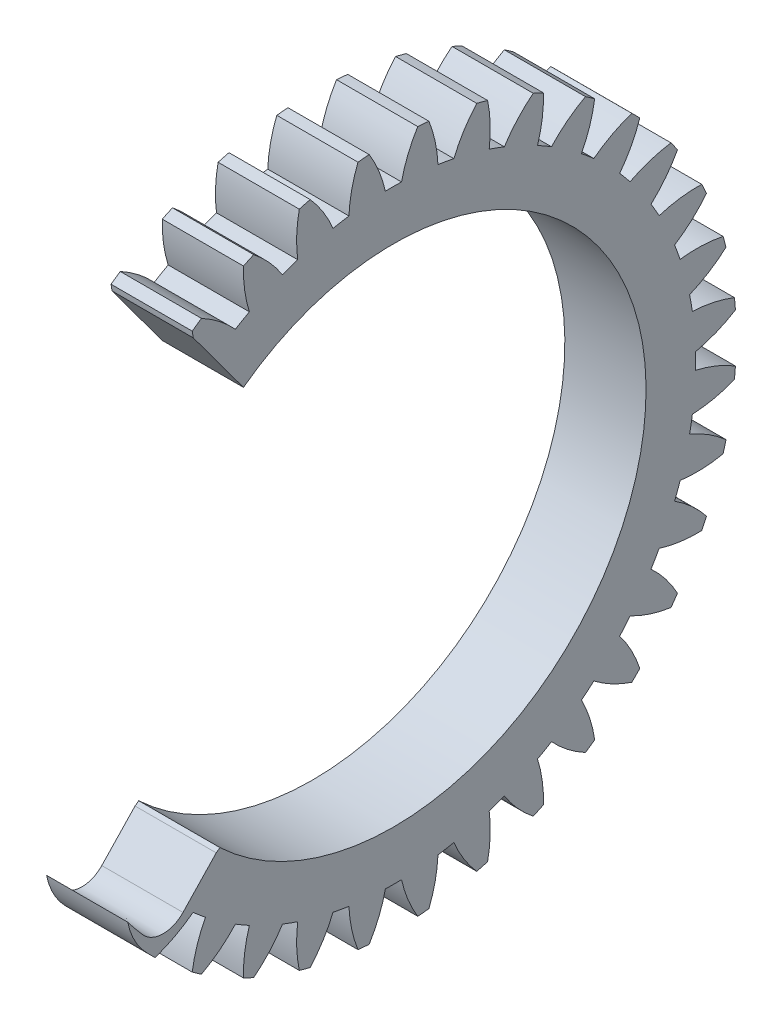
SolidWorks part; units mm, degrees
ref_plane "Plane1" through (0, 0, 0) normal (0, 0, 1) x (1, 0, 0)
ref_plane "Plane2" through (0, 0, 0) normal (0, 1, 0) x (1, 0, 0)
ref_plane "Plane3" through (0, 0, 0) normal (1, 0, 0) x (0, 0, -1)
sketch "HoldingSke" plane through (0, 0, 0) normal (0, 1, 0) x (1, 0, 0)
  line L0 (0, 0) -> (0.4045, -0.2939)
  line L1 (-15, 0) -> (100, 0) construction
  line L2 (0, 0) -> (-2.1039, 2.3779)
  line L3 (0, 0) -> (-11.863, 4.5341)
  line L4 (0, 0) -> (6.9867, 5.0761)
  line L5 (0, 0) -> (-46.8476, -17.4728)
  line L6 (0, 0) -> (-7.4607, -5.0337)
  line L7 (-2.1039, 2.3779) -> (8.6586, 51.2059)
  line L8 (-76.2, 54.61) -> (-71.9, 54.61)
  line L9 (-71.009, 38.7566) -> (-53.1078, 45.2721)
  line L10 (-76.2, 71.12) -> (104.1128, 71.12)
  line L11 (0, 0) -> (-9, 0)
  line L12 (-76.2, 101.6) -> (-76.133, 101.6)
  line L13 (24.9733, 27.94) -> (52.9518, 28.4284)
  line L14 (24.9733, 27.94) -> (24.9743, 27.94)
  line L15 (24.9733, 27.94) -> (100.4006, 29.5858)
  line L16 (-63.627, -2) -> (-12.827, -2)
  circle A0 centre (0, 0) radius 28
  circle A1 centre (0, 0) radius 33.499
  circle A2 centre (0, 0) radius 37.5
  circle A3 centre (0, 0) radius 28
  dimension "Num_teeth" = 36
  dimension "Pitch_radius" = 180.3128
  dimension "Width" = 9
  dimension "Thickness" = 9
sketch "BasProSke" plane through (0, 0, 0) normal (0, 1, 0) x (1, 0, 0)
  line L0 (-10, 0) -> (60, 0) construction
  line L1 (0, 0) -> (0, 38)
  line L2 (0, 0) -> (9, 0)
  line L3 (9, 0) -> (9, 38)
  line L4 (9, 38) -> (0, 38)
  dimension "Thickness" = 9
  dimension "Diameter" = 76
revolve "Base-Revolve" add sketch "BasProSke" angle 360 about L0
sketch "TooCutSke" plane through (0, 0, 0) normal (1, 0, 0) x (0, 0, -1)
  line L1 (0, 0) -> (0, 107) construction
  line L2 (0, 0) -> (-1.6875, 35.9604) construction
  line L3 (0, 0) -> (-6.2701, 71.6676) construction
  line L4 (-1.6875, 35.9604) -> (-3.135, 35.8338) construction
  arc A0 (0.8949, 33.487) -> (-0.8949, 33.487) centre (0, 0) ccw
  arc A1 (2.7061, 37.929) -> (-2.7061, 37.929) centre (0, 0) ccw
  circle A2 centre (0, 0) radius 36 construction
  circle A3 centre (0, 0) radius 33.8289 construction
  arc A4 (-0.8949, 33.487) -> (-2.7061, 37.929) centre (-14.9484, 30.347) ccw
  arc A5 (2.7061, 37.929) -> (0.8949, 33.487) centre (14.9484, 30.347) ccw
extrude "ToothCut" cut sketch "TooCutSke" along normal through all
fillet "Breaks" [suppressed] radius 0.04 tangent propagation no
fillet "RootFillets" [suppressed] radius 0.501
pattern_circular "TeethCuts" count 36 every 10 about axis through (-10, 0, 0) along (1, 0, 0) of "ToothCut", "RootFillets", "Breaks"
sketch "HubNeaOneSke" plane through (0, 0, 0) normal (-1, 0, 0) x (0, 0, 1)
  circle A0 centre (0, 0) radius 33.499
  dimension "Diameter" = 66.998
extrude "HubNearOne" [suppressed] add sketch "HubNeaOneSke" along normal blind 41.0001
sketch "HubNeaBotSke" plane through (0, 0, 0) normal (-1, 0, 0) x (0, 0, 1)
  circle A0 centre (0, 0) radius 33.499
  dimension "Diameter" = 66.998
extrude "HubNearBoth" [suppressed] add sketch "HubNeaBotSke" along normal blind 20.5
ref_plane "FarPln" through (9, 0, 0) normal (1, 0, 0) x (0, 0, -1)
sketch "HubFarSke" plane through (9, 0, 0) normal (1, 0, 0) x (0, 0, -1)
  circle A0 centre (0, 0) radius 33.499
  dimension "Diameter" = 66.998
extrude "HubFar" [suppressed] add sketch "HubFarSke" along normal blind 20.5
sketch "BorSke" plane through (0, 0, 0) normal (1, 0, 0) x (0, 0, -1)
  circle A0 centre (0, 0) radius 28
  dimension "Diameter" = 56
extrude "Bore" cut sketch "BorSke" along normal mid plane 100.0001
sketch "KeySke" plane through (0, 0, 0) normal (1, 0, 0) x (0, 0, -1)
  line L0 (-8, 0) -> (-8, 32.3)
  line L1 (-8, 32.3) -> (8, 32.3)
  line L2 (8, 32.3) -> (8, 0)
  line L3 (0, 0) -> (0, 34) construction
  line L4 (-8, 0) -> (8, 0)
  dimension "Width" = 16
extrude "Keyway" [suppressed] cut sketch "KeySke" along normal mid plane 100.0001
pattern_circular "Keyway2" [suppressed] count 2 every 90 about axis through (-10, 0, 0) along (1, 0, 0) reverse direction yes
sketch "Szkic1" plane through (0, 0, 0) normal (1, 0, 0) x (0, 0, -1)
  line L0 (0, 0) -> (-27.328, 37.0259)
  line L1 (-27.328, 37.0259) -> (-47.6164, -10.233)
  line L2 (-47.6164, -10.233) -> (0, 0)
extrude "Wytnij-wyciągnięcie1" cut sketch "Szkic1" along normal through all
sketch "Szkic2" plane through (0, 0, 0) normal (1, 0, 0) x (0, 0, -1)
  line L0 (-19.6433, -20.6493) -> (-23.3286, -24.5233) construction
  line L1 (-19.6433, -20.6493) -> (-23.3286, -24.5233)
  line L2 (-24.5118, 27.7159) -> (-14.2182, -16.6493)
  line L3 (-14.2182, -16.6493) -> (-19.6433, -20.6493)
  line L4 (-24.5118, 27.7159) -> (-50.9594, 25.255)
  line L5 (-50.9594, 25.255) -> (-37.7356, -29.3697)
  line L6 (-37.7356, -29.3697) -> (-27.7664, -24.4546)
  line L7 (-26.426, -27.3069) -> (-27.3069, -26.426)
  line L8 (-26.426, -27.3069) -> (-25.0675, -25.4318)
  arc A0 (-24.5118, 27.7159) -> (-27.7664, -24.4546) centre (0, 0) ccw construction
  arc A1 (-24.5118, 27.7159) -> (-27.7664, -24.4546) centre (0, 0) ccw
  arc A2 (-27.3069, -26.426) -> (-29.4473, -22.4022) centre (-21.7924, -20.9115) cw
  spline S0 degree 3 poles (302532.6808, 374985.6443) (8149.2203, 10610.2229) (-159.022, 73.103) (-27.1426, -24.9996) (-26.9606, -25.1074) (-26.5829, -25.2806) (-26.3868, -25.3469) (-25.9801, -25.4387) (-25.7711, -25.4633) (-25.3572, -25.469) (-25.1483, -25.4503) (-24.7384, -25.37) (-24.5404, -25.3094) (-24.158, -25.1482) (-23.9725, -25.0463) (121.6398, 75.6737) (-9024.0806, 12319.2747) (-292511.267, 383110.9401) knots -98.947846 -98.947846 -98.947846 -98.947846 0.125 0.125 0.25 0.25 0.375 0.375 0.5 0.5 0.625 0.625 0.75 0.75 0.875 0.875 107.384575 107.384575 107.384575 107.384575 only from (-27.7664, -24.4546) to (-23.3286, -24.5233) construction
  spline S1 degree 3 poles (-27.7664, -24.4546) (-27.6277, -24.6121) (-27.4749, -24.7523) (-27.1426, -24.9996) (-26.9606, -25.1074) (-26.5829, -25.2806) (-26.3868, -25.3469) (-25.9801, -25.4387) (-25.7711, -25.4633) (-25.3572, -25.469) (-25.1483, -25.4503) (-24.7384, -25.37) (-24.5404, -25.3094) (-24.158, -25.1482) (-23.9725, -25.0463) (-23.6312, -24.8102) (-23.4733, -24.6754) (-23.3286, -24.5233) knots 0 0 0 0 0.125 0.125 0.25 0.25 0.375 0.375 0.5 0.5 0.625 0.625 0.75 0.75 0.875 0.875 1 1 1 1
extrude "Wytnij-wyciągnięcie2" cut sketch "Szkic2" against normal blind 43 and the other way through all contours A1 L4 L5 L6 | A1 S1 L1 L3 L2 region at (0, -1.5762, 26.5296) region at (0, 4.8425, 39.1923)
extrude "Dodanie-wyciągnięcie1" add sketch "Szkic2<3>" along normal up to surface (9 mm away) contours A2 L6 A1 | S1 L6 A2 L7 L8 region at (0, -25.7946, 26.8655) region at (0, -23.8723, 28.649) up to face at (9, -1.2954, -9.9994)
sketch "Szkic2<3>" plane through (0, 0, 0) normal (1, 0, 0) x (0, 0, -1) same geometry as "Szkic2"
equation "' \"Module@HoldingSke\" = 6.35"
equation "' \"Num_teeth@HoldingSke\" = 12"
equation "' \"Ap@HoldingSke\" =  20"
equation "' \"Ap@HoldingSke\" = 20"
equation "' \"Width@HoldingSke\" = 0.5 * 25.4"
equation "' \"Hub_dia@HoldingSke\"= 1 * 25.4"
equation "' \"Hub_dia@HoldingSke\" = 1 * 25.4"
equation "' \"Overall_len@HoldingSke\" = 1.0 * 25.4"
equation "' \"Bore@HoldingSke\" = 0.75 * 25.4"
equation "' \"T_dim@HoldingSke\" = 0.1 * 25.4"
equation "' \"Width@KeySke\" = 0.25 * 25.4"
equation "' \"Show_teeth@HoldingSke\" = 13"
equation "' \"Backlash@HoldingSke\" = 0.009 * 25.4"
equation "' \"Addendum_fac@HoldingSke\" = 1.0"
equation "' \"Dedendum_fac@HoldingSke\" = 1.25"
equation "' \"Dedendum_add@HoldingSke\" = 0.00005 * 25.4"
equation "' \"Clearance_fac@HoldingSke\" = 0.25"
equation "\"Pitch@HoldingSke\" = 1 / \"Module@HoldingSke\""
equation "\"Overcut_dia@TooCutSke\" = (\"Num_teeth@HoldingSke\" + 2 * \"Addendum_fac@HoldingSke\") / \"Pitch@HoldingSke\" + 0.002 * 25.4"
equation "\"Pitch_dia@TooCutSke\" = \"Num_teeth@HoldingSke\" / \"Pitch@HoldingSke\""
equation "\"Base_dia@TooCutSke\" = \"Num_teeth@HoldingSke\" / \"Pitch@HoldingSke\" * cos((\"Ap@HoldingSke\"  * 3.14159265 / 180))"
equation "\"Root_dia@TooCutSke\" = (\"Num_teeth@HoldingSke\" + 2) / \"Pitch@HoldingSke\" - 2 * (\"Addendum_fac@HoldingSke\" + \"Dedendum_fac@HoldingSke\") / \"Pitch@HoldingSke\" - \"Dedendum_add@HoldingSke\" * 2"
equation "\"Half_ang@TooCutSke\" = 180 / \"Num_teeth@HoldingSke\""
equation "\"Half_CT@TooCutSke\" = \"Num_teeth@HoldingSke\" / \"Pitch@HoldingSke\" * sin((3.14159265 / 2 / \"Num_teeth@HoldingSke\")) / 2 - 7 * \"Backlash@HoldingSke\" / 4"
equation "\"Flank_rad@TooCutSke\" = \"Num_teeth@HoldingSke\" / \"Pitch@HoldingSke\" / 5"
equation "\"Radius@RootFillets\" = \"Clearance_fac@HoldingSke\" / \"Pitch@HoldingSke\" + \"Dedendum_add@HoldingSke\""
equation "\"Break_rad@Breaks\" = 0.02 / \"Pitch@HoldingSke\""
equation "\"Thickness@HoldingSke\" = \"Width@HoldingSke\""
equation "\"OAL@HoldingSke\" = \"Thickness@HoldingSke\""
equation "\"MHD@HoldingSke\" = (\"Num_teeth@HoldingSke\" + 2) / \"Pitch@HoldingSke\" - 2 * (\"Addendum_fac@HoldingSke\" + \"Dedendum_fac@HoldingSke\")  / \"Pitch@HoldingSke\" - \"Dedendum_add@HoldingSke\" * 2"
equation "\"MBD@HoldingSke\" = (\"Num_teeth@HoldingSke\" + 2) / \"Pitch@HoldingSke\" - 2 * (\"Addendum_fac@HoldingSke\" + \"Dedendum_fac@HoldingSke\")  / \"Pitch@HoldingSke\" - \"Dedendum_add@HoldingSke\" * 2 - 0.002 * 25.4"
equation "\"MHD@HoldingSke\" = ((sgn( \"MHD@HoldingSke\" - \"Hub_dia@HoldingSke\" )-1)*( \"MHD@HoldingSke\" - \"Hub_dia@HoldingSke\" ))/-2+ \"Hub_dia@HoldingSke\""
equation "\"MBD@HoldingSke\" = ((sgn( \"MBD@HoldingSke\" - \"Bore@HoldingSke\" )-1)*( \"MBD@HoldingSke\" - \"Bore@HoldingSke\" ))/-2+ \"Bore@HoldingSke\""
equation "\"OAL@HoldingSke\" = ((sgn( \"OAL@HoldingSke\" - \"Overall_len@HoldingSke\" )+1)*( \"OAL@HoldingSke\" - \"Overall_len@HoldingSke\" ))/2 + \"Overall_len@HoldingSke\" + 0.000002 * 25.4"
equation "\"Num_teeth@TeethCuts\" = int( \"Show_teeth@HoldingSke\" ) + 1"
equation "\"Num_teeth@TeethCuts\" = ((sgn( \"Num_teeth@TeethCuts\" - \"Num_teeth@HoldingSke\" )-1)*( \"Num_teeth@TeethCuts\" - \"Num_teeth@HoldingSke\" ))/-2+ \"Num_teeth@HoldingSke\""
equation "\"Num_teeth@TeethCuts\" = ((sgn( \"Num_teeth@TeethCuts\" - 2.0)+1)*( \"Num_teeth@TeethCuts\" - 2.0))/2 +2.0"
equation "\"Angle@TeethCuts\" = 360.0 / \"Num_teeth@HoldingSke\""
equation "\"Diameter@BasProSke\" = (\"Num_teeth@HoldingSke\" + 2 * \"Addendum_fac@HoldingSke\") / \"Pitch@HoldingSke\""
equation "\"Thickness@BasProSke\"  = \"Thickness@HoldingSke\""
equation "' \"Fillet_rad@BasProSke\" =  \"Thickness@HoldingSke\" * 0.05"
equation "' \"Fillet_rad@BasProSke\" = \"Thickness@HoldingSke\" * 0.05"
equation "\"MHD@HoldingSke\" = ((sgn( \"MHD@HoldingSke\" - \"Root_dia@TooCutSke\" )-1)*( \"MHD@HoldingSke\" - \"Root_dia@TooCutSke\" ))/-2+ \"Root_dia@TooCutSke\""
equation "\"Diameter@HubNeaOneSke\" = \"MHD@HoldingSke\""
equation "\"Length@HubNearOne\" = \"OAL@HoldingSke\" - \"Thickness@BasProSke\""
equation "\"Diameter@HubNeaBotSke\" = \"MHD@HoldingSke\""
equation "\"Length@HubNearBoth\" = ( \"OAL@HoldingSke\" - \"Thickness@BasProSke\" ) / 2.0"
equation "\"Thickness@FarPln\" = \"Thickness@BasProSke\""
equation "\"Diameter@HubFarSke\" = \"MHD@HoldingSke\""
equation "\"Length@HubFar\" = ( \"OAL@HoldingSke\" - \"Thickness@BasProSke\" ) / 2.0"
equation "\"Diameter@BorSke\" = \"MBD@HoldingSke\""
equation "\"D1@Bore\" = \"OAL@HoldingSke\" * 2.0"
equation "\"D1@Keyway\" = \"OAL@HoldingSke\" * 2.0"
equation "\"Offset@KeySke\" = \"T_dim@HoldingSke\" + \"MBD@HoldingSke\" / 2.0"
